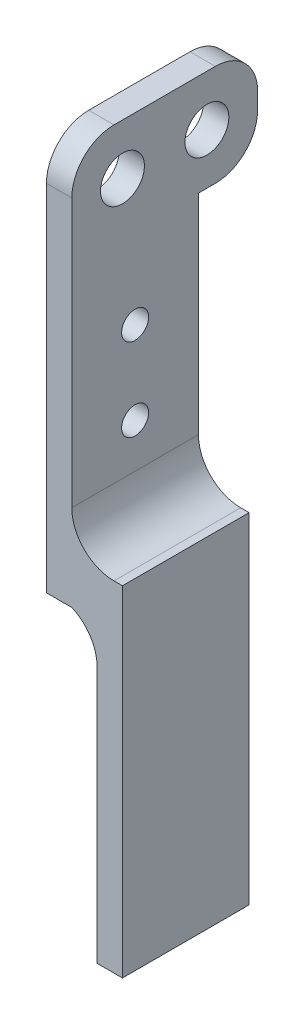
SolidWorks part; units mm, degrees
ref_plane "Front Plane" through (0, 0, 0) normal (0, 0, 1) x (1, 0, 0)
ref_plane "Top Plane" through (0, 0, 0) normal (0, 1, 0) x (1, 0, 0)
ref_plane "Right Plane" through (0, 0, 0) normal (1, 0, 0) x (0, 0, -1)
sketch "Sketch1" plane through (0, 0, 0) normal (1, 0, 0) x (0, 0, -1)
  line L0 (0, 0) -> (10, 0) construction
  line L1 (55, 0) -> (-55, 0) construction
  line L3 (-6, -6) -> (16, -6)
  line L4 (-6, -6) -> (-6, 6)
  line L5 (-6, 6) -> (16, 6)
  line L6 (16, -6) -> (16, 6)
  line L7 (-6, -6) -> (16, 6) construction
  line L8 (-6, 6) -> (16, -6) construction
  circle A0 centre (10, 0) radius 2.6
  circle A1 centre (0, 0) radius 2.6
  point P5 (5, 0)
  dimension "D4" = 5.2
  dimension "D5" = 5.2
  dimension "D1" = 10
  dimension "D2" = 22
  dimension "D3" = 12
extrude "Boss-Extrude1" add sketch "Sketch1" along normal blind 3
sketch "Sketch2" plane through (0, 0, 0) normal (1, 0, 0) x (0, 0, -1)
  line L1 (-6, -6) -> (9, -6)
  line L2 (-6, -6) -> (-6, -42)
  line L3 (-6, -42) -> (9, -42)
  line L4 (9, -6) -> (9, -42)
  dimension "D1" = 15
  dimension "D2" = 36
extrude "Boss-Extrude2" add sketch "Sketch2" along normal blind 3
fillet "Fillet1" radius 5 3 edges at (1.5, 6, 6) (1.5, -6, -16) (1.5, 6, -16)
fillet "Fillet2" radius 1 2 edges at (1.5, -42, 6) (1.5, -42, -9)
sketch "Sketch3" plane through (3, 0, 0) normal (1, 0, 0) x (0, 0, -1)
sketch "Sketch4" plane through (3, 0, 0) normal (1, 0, 0) x (0, 0, -1)
  line L0 (9, -41) -> (9, -6) construction
  line L1 (9, -6.7137) -> (-6, -6.7137)
  line L2 (9, -6.7137) -> (9, -41)
  line L3 (9, -41) -> (-6, -41)
  line L4 (-6, -6.7137) -> (-6, -41)
extrude "Boss-Extrude3" add sketch "Sketch4" along normal blind 12.2
sketch "Sketch7" plane through (0, -6.7137, 0) normal (0, 1, 0) x (1, 0, 0)
  line L1 (3, 9) -> (15.2, 9)
  line L2 (3, 9) -> (3, -6)
  line L3 (3, -6) -> (15.2, -6)
  line L4 (15.2, 9) -> (15.2, -6)
extrude "Cut-Extrude3" cut sketch "Sketch7" against normal blind 50
sketch "Sketch8" plane through (3, 0, 0) normal (1, 0, 0) x (0, 0, -1)
  line L0 (9, -41) -> (9, -6) construction
  line L1 (1.5, -25.55) -> (1.5, -15.75)
  circle A0 centre (1.5, -15.75) radius 1.6
  circle A1 centre (1.5, -25.55) radius 1.6
  dimension "D3" = 3.2
  dimension "D4" = 3.2
  dimension "D1" = 7.5
  dimension "D2" = 9.8
extrude "Cut-Extrude4" cut sketch "Sketch8" against normal blind 10 contours A0 | A1 L1 | A1 L1 region at (3, -14.6506, -0.4006) region at (3, -24.4506, -2.5994)
sketch "Sketch9" plane through (3, 0, 0) normal (1, 0, 0) x (0, 0, -1)
  line L0 (1.5, -25.55) -> (1.5, -35.77) construction
  line L1 (-6, 1) -> (-6, -41) construction
  line L2 (-6, -35.77) -> (9, -35.77)
  line L3 (-6, -35.77) -> (-6, -41)
  line L4 (-6, -41) -> (9, -41)
  line L5 (9, -35.77) -> (9, -41)
  dimension "D1" = 10.22
extrude "Boss-Extrude4" add sketch "Sketch9" along normal blind 6
sketch "Sketch10" plane through (0, -41, 0) normal (0, -1, 0) x (-1, 0, 0)
  line L0 (-9, 9) -> (-3, 9) construction
  line L1 (-9, -6) -> (-6, -6)
  line L2 (-9, -6) -> (-9, 9)
  line L3 (-9, 9) -> (-6, 9)
  line L4 (-6, -6) -> (-6, 9)
extrude "Boss-Extrude5" add sketch "Sketch10" along normal blind 35
fillet "Fillet3" radius 5 1 edges at (6, -41, -1.5)
fillet "Fillet4" radius 5 1 edges at (3, -35.77, -1.5)
sketch "Sketch11" plane through (3, 0, 0) normal (1, 0, 0) x (0, 0, -1)
  line L1 (-6, -41) -> (9.0338, -41)
  line L2 (-6, -41) -> (-6, -43.0207)
  line L3 (-6, -43.0207) -> (9.0338, -43.0207)
  line L4 (9.0338, -41) -> (9.0338, -43.0207)
extrude "Cut-Extrude5" cut sketch "Sketch11" against normal blind 3
